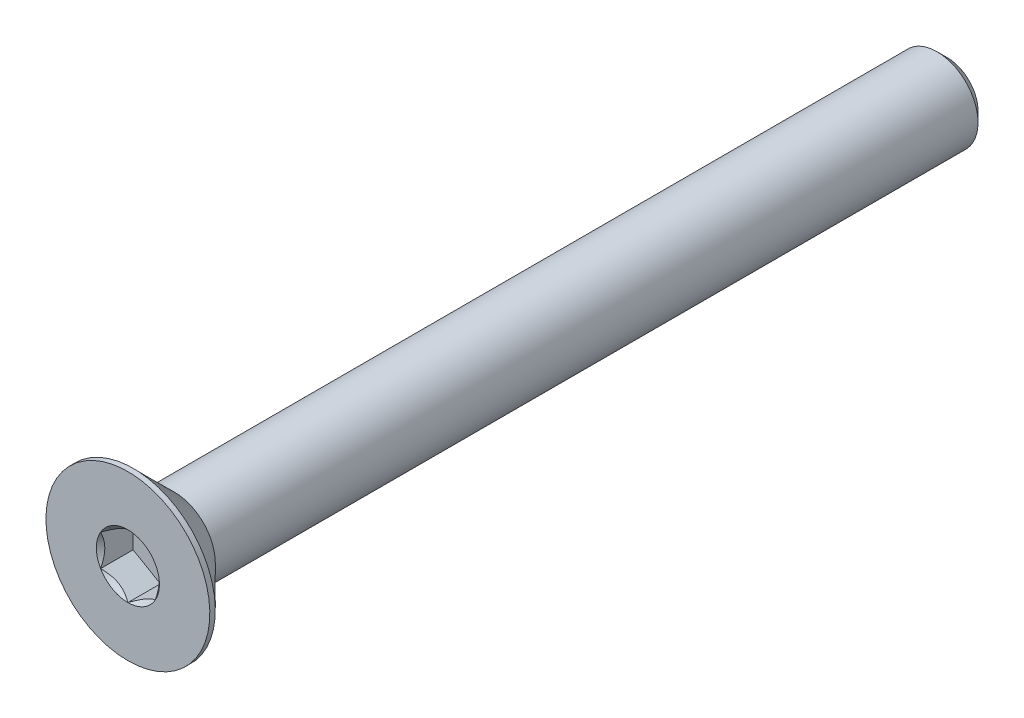
SolidWorks part; units mm, degrees
material "Alloy Steel"
ref_plane "Front" through (0, 0, 0) normal (0, 0, 1) x (1, 0, 0)
ref_plane "Top" through (0, 0, 0) normal (0, 1, 0) x (1, 0, 0)
ref_plane "Right" through (0, 0, 0) normal (1, 0, 0) x (0, 0, -1)
sketch "Sketch1" plane through (0, 0, 0) normal (1, 0, 0) x (0, 0, -1)
  line L0 (0, 3) -> (0.2, 3) construction
  line L1 (0.2, 3) -> (1.7, 1.5) construction
  line L2 (0, 1.5) -> (30, 1.5)
  line L3 (30, 1.5) -> (30, 0)
  line L4 (30, 0) -> (0, 0)
  line L5 (0, 0) -> (0, 3) construction
  line L6 (0, 3) -> (0, -3) construction
  line L7 (30, 1.5) -> (30, -1.5) construction
  line L8 (0, -3) -> (0.2, -3) construction
  line L9 (0.2, -3) -> (1.7, -1.5) construction
  line L11 (0, 1.5) -> (0, 0)
  line L12 (1.7, 1.5) -> (1.7, 0) construction
revolve "Revolve1" add sketch "Sketch1" angle 360 mid plane about L4
sketch "Sketch3" plane through (0, 0, -30) normal (0, 0, -1) x (-1, 0, 0)
  circle A0 centre (0, 0) radius 1.5
curve "Helix/Spiral1" pitch 0.5 height 30 turns 60
sketch "Sketch2" plane through (0, 0, 0) normal (1, 0, 0) x (0, 0, -1)
  line L0 (30, 1.5) -> (30.4375, 1.5)
  line L1 (30.4375, 1.5) -> (30.25, 1.1752)
  line L2 (30.25, 1.1752) -> (30.1875, 1.1752)
  line L3 (30.1875, 1.1752) -> (30, 1.5)
  line L4 (30.0938, 1.3376) -> (30.3438, 1.3376) construction
  dimension "D1" = 60
  dimension "D2" = 0.0625
  dimension "D3" = 0.25
chamfer "Chamfer1" distance 0.375 angle 45 1 edges at (0, 1.5, -30)
sweep "Cut-Sweep1" [suppressed] cut profiles "Sketch2" path "Helix/Spiral1"
sketch "Sketch7" plane through (0, 0, 0) normal (1, 0, 0) x (0, 0, -1)
  line L0 (0, 3) -> (0.2, 3) construction
  line L1 (0.2, 3) -> (1.7, 1.5) construction
  line L2 (0, 3) -> (0.2, 3)
  line L3 (0.2, 3) -> (1.7, 1.5)
  line L4 (1.7, 1.5) -> (1.7, 0) construction
  line L5 (1.7, 1.5) -> (1.7, 0)
  line L7 (0, 0) -> (0, 3) construction
  line L8 (0, 0) -> (0, 3)
  line L9 (0, 0) -> (1.7, 0)
  line L10 (3.3, 0) -> (-3.3, 0) construction
revolve "Revolve2" add sketch "Sketch7" angle 360 mid plane about L9
ref_plane "Plane1" through (0, 0, -1.7) normal (0, 0, 1) x (1, 0, 0)
sketch "Sketch8" plane through (0, 0, -1.7) normal (0, 0, 1) x (1, 0, 0)
  circle A0 centre (0, 0) radius 1.5
extrude "Boss-Extrude1" add sketch "Sketch8" against normal through all draft 45
sketch "Sketch5" plane through (0, 0, 0) normal (0, 0, 1) x (1, 0, 0)
  line L1 (1, -0.5774) -> (1, 0.5774)
  line L2 (1, 0.5774) -> (0, 1.1547)
  line L3 (0, 1.1547) -> (-1, 0.5774)
  line L4 (-1, 0.5774) -> (-1, -0.5774)
  line L5 (-1, -0.5774) -> (0, -1.1547)
  line L6 (0, -1.1547) -> (1, -0.5774)
  circle A0 centre (0, 0) radius 1 construction
  dimension "Hex" = 2
extrude "Cut-Extrude2" cut sketch "Sketch5" against normal blind 1.19
sketch "Sketch6" plane through (0, 0, 0) normal (0, 0, 1) x (1, 0, 0)
  circle A0 centre (0, 0) radius 1.1547
extrude "Cut-Extrude3" cut sketch "Sketch6" against normal blind 1.19 draft 45
sketch "Sketch9" [suppressed] plane through (0, 0, -1.5) normal (0, 0, 1) x (1, 0, 0)
  circle A1 centre (0, 0) radius 1.25
  circle A2 centre (0, 0) radius 1.25
  point P0 (0, 1.25)
  dimension "D1" = 0
extrude "Boss-Extrude2" [suppressed] add sketch "Sketch9" against normal offset from surface (3.5 mm away) 26
fillet "Fillet1" [suppressed] radius 0.3
sketch "Sketch10" plane through (0, 0, 0) normal (1, 0, 0) x (0, 0, -1)
  line L0 (30, 1.5) -> (30, -1.5) construction
  point P0 (29.25, -1.5)
  dimension "D1" = 0.75
equation "\"D3@Helix/Spiral1\" = \"Lg@Sketch1\""
equation "\"D2@Sketch2\" = \"D4@Helix/Spiral1\" * .125"
equation "\"D3@Sketch2\" = \"D4@Helix/Spiral1\" * .5"
equation "\"D1@Chamfer1\" = \"D4@Helix/Spiral1\" * .75"
equation "\"D1@Cut-Extrude2\" = \"Head Ht@Sketch1\" * .7"
equation "\"D1@Sketch10\" = \"D4@Helix/Spiral1\" * 1.5"
equation "\"D1@Cut-Extrude3\" = \"D1@Cut-Extrude2\""
equation "\"D1@Fillet1\" = \"Dia@Sketch1\" * .1"
